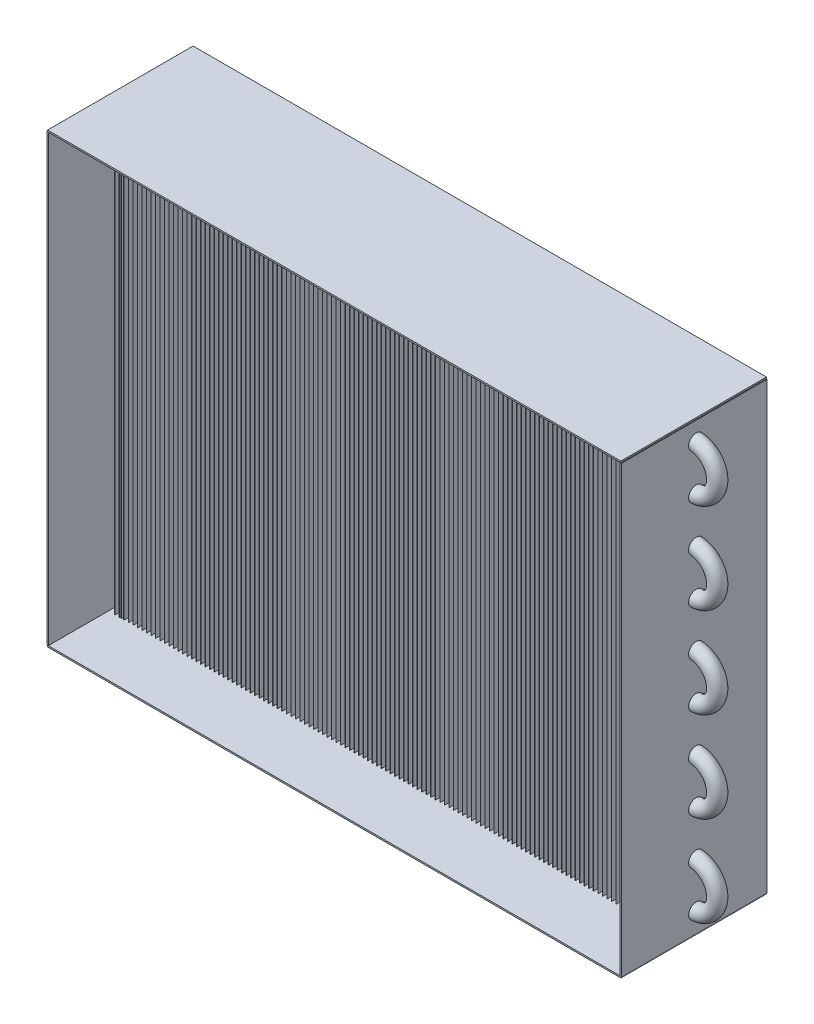
SolidWorks part; units mm, degrees
ref_plane "Front Plane" through (0, 0, 0) normal (0, 0, 1) x (1, 0, 0)
ref_plane "Top Plane" through (0, 0, 0) normal (0, 1, 0) x (1, 0, 0)
ref_plane "Right Plane" through (0, 0, 0) normal (1, 0, 0) x (0, 0, -1)
sketch "Sketch2" plane through (0, 0, 0) normal (0, 0, 1) x (1, 0, 0)
  line L0 (0, 16.0001) -> (380, 16.0001)
  line L2 (380, -13.9999) -> (0, -13.9999)
  line L4 (0, -43.9999) -> (380, -43.9999)
  line L6 (380, -73.9999) -> (0, -73.9999)
  line L8 (0, -103.9999) -> (380, -103.9999)
  line L10 (380, -133.9999) -> (0, -133.9999)
  line L12 (0, -163.9999) -> (380, -163.9999)
  line L14 (380, -193.9999) -> (0, -193.9999)
  line L16 (0, -223.9999) -> (380, -223.9999)
  line L18 (380, -253.9999) -> (0, -253.9999)
  arc A0 (380, -13.9999) -> (380, 16.0001) centre (380, 1.0001) ccw
  arc A1 (380, -73.9999) -> (380, -43.9999) centre (380, -58.9999) ccw
  arc A2 (380, -133.9999) -> (380, -103.9999) centre (380, -118.9999) ccw
  arc A3 (380, -193.9999) -> (380, -163.9999) centre (380, -178.9999) ccw
  arc A4 (380, -253.9999) -> (380, -223.9999) centre (380, -238.9999) ccw
  arc A5 (0, -193.9999) -> (0, -223.9999) centre (0, -208.9999) ccw
  arc A6 (0, -133.9999) -> (0, -163.9999) centre (0, -148.9999) ccw
  arc A7 (0, -73.9999) -> (0, -103.9999) centre (0, -88.9999) ccw
  arc A8 (0, -13.9999) -> (0, -43.9999) centre (0, -28.9999) ccw
sweep "Sweep1" add path "Sketch2" circular profile diameter 10 parameters "D3"=10
ref_plane "Plane1" through (0, 0, 0) normal (-1, 0, 0) x (0, 0, 1)
sketch "Sketch11" plane through (0, 0, 0) normal (-1, 0, 0) x (0, 0, 1)
  line L1 (-47.2003, 28.3122) -> (49.5408, 28.3122)
  line L2 (-47.2003, 28.3122) -> (-47.2003, -267.1774)
  line L3 (-47.2003, -267.1774) -> (49.5408, -267.1774)
  line L4 (49.5408, 28.3122) -> (49.5408, -267.1774)
ref_plane "Plane2" through (380, 0, 0) normal (1, 0, 0) x (0, 0, -1)
sketch "Sketch12" plane through (380, 0, 0) normal (1, 0, 0) x (0, 0, -1)
  line L1 (-49.5408, 28.3122) -> (47.2003, 28.3122)
  line L2 (-49.5408, 28.3122) -> (-49.5408, -267.1774)
  line L3 (-49.5408, -267.1774) -> (47.2003, -267.1774)
  line L4 (47.2003, 28.3122) -> (47.2003, -267.1774)
extrude "Boss-Extrude1" add sketch "Sketch12" along normal blind 1
extrude "Boss-Extrude2" add sketch "Sketch11" along normal blind 1 contours L2 L3 L4 L1
sketch "Sketch13" plane through (0, 0, 0) normal (-1, 0, 0) x (0, 0, 1)
  line L0 (0, -9.0249) -> (0, 15.9751)
  circle A0 centre (0, 15.9751) radius 5
  spline S1 degree 3 poles (-2.1721, -18.5634) (-1.5588, -18.8112) (-1.2431, -18.9036) (-0.5936, -19.0256) (-0.2669, -19.0536) (0.2222, -19.0478) (0.3852, -19.0378) (0.7115, -19.0017) (0.8755, -18.9752) (1.3573, -18.8726) (1.668, -18.7736) (2.2686, -18.5152) (2.5604, -18.3538) (3.0985, -17.983) (3.3478, -17.7727) (3.6916, -17.4193) (3.8014, -17.2947) (4.0059, -17.0383) (4.1013, -16.9057) (4.3676, -16.4955) (4.519, -16.2039) (4.7638, -15.5911) (4.8545, -15.2774) (4.9744, -14.6359) (5.0034, -14.3043) (4.996, -13.649) (4.9606, -13.3249) (4.8263, -12.6838) (4.7263, -12.3662) (4.4703, -11.7657) (4.3139, -11.4791) (3.9421, -10.9343) (3.7306, -10.6823) (3.265, -10.2257) (3.0072, -10.0182) (2.4566, -9.6585) (2.1673, -9.5079) (1.561, -9.2639) (1.2409, -9.1705) (0.5982, -9.0501) (0.2733, -9.0216) (-0.2194, -9.0271) (-0.3851, -9.0371) (-0.7114, -9.0732) (-0.8727, -9.0991) (-1.3513, -9.2002) (-1.6642, -9.2988) (-2.2712, -9.559) (-2.5571, -9.7168) (-3.0951, -10.086) (-3.3497, -10.3002) (-3.8072, -10.7697) (-4.0108, -11.0243) (-4.3678, -11.5732) (-4.5211, -11.869) (-4.7632, -12.4752) (-4.8544, -12.7886) (-4.9753, -13.4365) (-5.0034, -13.7648) (-4.9959, -14.4168) (-4.9602, -14.7452) (-4.8247, -15.3894) (-4.7266, -15.7005) (-4.4708, -16.3016) (-4.311, -16.594) (-3.9423, -17.1346) (-3.7334, -17.3849) (-3.3825, -17.7301) (-3.2585, -17.8406) (-3.0027, -18.0468) (-2.8705, -18.143) (-2.4614, -18.4114) (-2.1721, -18.5634) (-1.5588, -18.8112) (-1.2431, -18.9036) knots -0.03125 -0.03125 0 0 0.03125 0.03125 0.0625 0.0625 0.078125 0.078125 0.09375 0.09375 0.125 0.125 0.15625 0.15625 0.1875 0.1875 0.203125 0.203125 0.21875 0.21875 0.25 0.25 0.28125 0.28125 0.3125 0.3125 0.34375 0.34375 0.375 0.375 0.40625 0.40625 0.4375 0.4375 0.46875 0.46875 0.5 0.5 0.53125 0.53125 0.5625 0.5625 0.578125 0.578125 0.59375 0.59375 0.625 0.625 0.65625 0.65625 0.6875 0.6875 0.71875 0.71875 0.75 0.75 0.78125 0.78125 0.8125 0.8125 0.84375 0.84375 0.875 0.875 0.90625 0.90625 0.9375 0.9375 0.953125 0.953125 0.96875 0.96875 1 1 1.03125 1.03125 1.0625 only from (-1.8655, -18.6873) to (-1.8655, -18.6873) construction
sketch "Sketch15" plane through (0, 0, 0) normal (-1, 0, 0) x (0, 0, 1)
  line L0 (0, -9.0249) -> (0, 15.9751)
  circle A0 centre (0, 15.9751) radius 5
  spline S0 degree 3 poles (-2.1721, -18.5634) (-1.5588, -18.8112) (-1.2431, -18.9036) (-0.5936, -19.0256) (-0.2669, -19.0536) (0.2222, -19.0478) (0.3852, -19.0378) (0.7115, -19.0017) (0.8755, -18.9752) (1.3573, -18.8726) (1.668, -18.7736) (2.2686, -18.5152) (2.5604, -18.3538) (3.0985, -17.983) (3.3478, -17.7727) (3.6916, -17.4193) (3.8014, -17.2947) (4.0059, -17.0383) (4.1013, -16.9057) (4.3676, -16.4955) (4.519, -16.2039) (4.7638, -15.5911) (4.8545, -15.2774) (4.9744, -14.6359) (5.0034, -14.3043) (4.996, -13.649) (4.9606, -13.3249) (4.8263, -12.6838) (4.7263, -12.3662) (4.4703, -11.7657) (4.3139, -11.4791) (3.9421, -10.9343) (3.7306, -10.6823) (3.265, -10.2257) (3.0072, -10.0182) (2.4566, -9.6585) (2.1673, -9.5079) (1.561, -9.2639) (1.2409, -9.1705) (0.5982, -9.0501) (0.2733, -9.0216) (-0.2194, -9.0271) (-0.3851, -9.0371) (-0.7114, -9.0732) (-0.8727, -9.0991) (-1.3513, -9.2002) (-1.6642, -9.2988) (-2.2712, -9.559) (-2.5571, -9.7168) (-3.0951, -10.086) (-3.3497, -10.3002) (-3.8072, -10.7697) (-4.0108, -11.0243) (-4.3678, -11.5732) (-4.5211, -11.869) (-4.7632, -12.4752) (-4.8544, -12.7886) (-4.9753, -13.4365) (-5.0034, -13.7648) (-4.9959, -14.4168) (-4.9602, -14.7452) (-4.8247, -15.3894) (-4.7266, -15.7005) (-4.4708, -16.3016) (-4.311, -16.594) (-3.9423, -17.1346) (-3.7334, -17.3849) (-3.3825, -17.7301) (-3.2585, -17.8406) (-3.0027, -18.0468) (-2.8705, -18.143) (-2.4614, -18.4114) (-2.1721, -18.5634) (-1.5588, -18.8112) (-1.2431, -18.9036) knots -0.03125 -0.03125 0 0 0.03125 0.03125 0.0625 0.0625 0.078125 0.078125 0.09375 0.09375 0.125 0.125 0.15625 0.15625 0.1875 0.1875 0.203125 0.203125 0.21875 0.21875 0.25 0.25 0.28125 0.28125 0.3125 0.3125 0.34375 0.34375 0.375 0.375 0.40625 0.40625 0.4375 0.4375 0.46875 0.46875 0.5 0.5 0.53125 0.53125 0.5625 0.5625 0.578125 0.578125 0.59375 0.59375 0.625 0.625 0.65625 0.65625 0.6875 0.6875 0.71875 0.71875 0.75 0.75 0.78125 0.78125 0.8125 0.8125 0.84375 0.84375 0.875 0.875 0.90625 0.90625 0.9375 0.9375 0.953125 0.953125 0.96875 0.96875 1 1 1.03125 1.03125 1.0625 only from (-1.8655, -18.6873) to (-1.8655, -18.6873) construction
extrude "Cut-Extrude2" cut sketch "Sketch15" along normal blind 1 contours A0
sketch "Sketch16" plane through (0, 0, 0) normal (-1, 0, 0) x (0, 0, 1)
  line L0 (0, -228.9749) -> (0, -253.9749)
  circle A0 centre (0, -253.9749) radius 5
  spline S0 degree 3 poles (-3.0361, -227.96) (-2.4848, -228.3255) (-2.194, -228.4793) (-1.5824, -228.7291) (-1.2678, -228.8223) (-0.7875, -228.9151) (-0.6258, -228.9383) (-0.2991, -228.9687) (-0.1332, -228.9758) (0.3597, -228.9728) (0.684, -228.9386) (1.3244, -228.8072) (1.6429, -228.7083) (2.2449, -228.4539) (2.5316, -228.2983) (2.9396, -228.0216) (3.0722, -227.9217) (3.3243, -227.7117) (3.4444, -227.6011) (3.7877, -227.2527) (3.9946, -226.9974) (4.3571, -226.446) (4.5086, -226.1568) (4.7542, -225.5522) (4.8487, -225.2331) (4.972, -224.5894) (5.0018, -224.2648) (4.998, -223.6098) (4.9634, -223.2787) (4.8324, -222.6392) (4.7364, -222.3272) (4.4815, -221.7191) (4.3248, -221.4296) (3.9605, -220.8887) (3.75, -220.6336) (3.2832, -220.17) (3.0302, -219.9639) (2.4859, -219.6024) (2.1914, -219.4461) (1.5863, -219.1981) (1.2739, -219.1044) (0.7902, -219.0102) (0.6259, -218.9866) (0.299, -218.9561) (0.1358, -218.949) (-0.3533, -218.9517) (-0.6796, -218.9854) (-1.3265, -219.1185) (-1.6383, -219.2159) (-2.2392, -219.4699) (-2.5315, -219.6288) (-3.0737, -219.9973) (-3.3241, -220.2061) (-3.7837, -220.6723) (-3.9931, -220.9314) (-4.352, -221.4768) (-4.5043, -221.7655) (-4.7529, -222.3757) (-4.8465, -222.6918) (-4.9704, -223.332) (-5.0015, -223.6608) (-4.9984, -224.3191) (-4.9649, -224.6437) (-4.8351, -225.2838) (-4.7372, -225.6024) (-4.4846, -226.206) (-4.33, -226.4931) (-4.0553, -226.9015) (-3.9559, -227.0345) (-3.7465, -227.2878) (-3.6363, -227.4085) (-3.2891, -227.7532) (-3.0361, -227.96) (-2.4848, -228.3255) (-2.194, -228.4793) knots -0.03125 -0.03125 0 0 0.03125 0.03125 0.0625 0.0625 0.078125 0.078125 0.09375 0.09375 0.125 0.125 0.15625 0.15625 0.1875 0.1875 0.203125 0.203125 0.21875 0.21875 0.25 0.25 0.28125 0.28125 0.3125 0.3125 0.34375 0.34375 0.375 0.375 0.40625 0.40625 0.4375 0.4375 0.46875 0.46875 0.5 0.5 0.53125 0.53125 0.5625 0.5625 0.578125 0.578125 0.59375 0.59375 0.625 0.625 0.65625 0.65625 0.6875 0.6875 0.71875 0.71875 0.75 0.75 0.78125 0.78125 0.8125 0.8125 0.84375 0.84375 0.875 0.875 0.90625 0.90625 0.9375 0.9375 0.953125 0.953125 0.96875 0.96875 1 1 1.03125 1.03125 1.0625 only from (-2.7604, -228.1428) to (-2.7604, -228.1428) construction
ref_plane "Plane3" through (0, 28.3122, 0) normal (0, 1, 0) x (1, 0, 0)
sketch "Sketch17" plane through (0, 28.3122, 0) normal (0, 1, 0) x (1, 0, 0)
  line L0 (-1, -49.5408) -> (0, -49.5408) construction
  line L1 (-0.5, -49.5408) -> (380.5, -49.5408)
  line L2 (-0.5, -49.5408) -> (-0.5, 47.2003)
  line L3 (-0.5, 47.2003) -> (380.5, 47.2003)
  line L4 (380.5, -49.5408) -> (380.5, 47.2003)
  line L5 (381, 47.2003) -> (380, 47.2003) construction
extrude "Boss-Extrude4" add sketch "Sketch17" along normal blind 1
ref_plane "Plane5" through (0, -267.1774, 0) normal (0, -1, 0) x (-1, 0, 0)
sketch "Sketch18" plane through (0, -267.1774, 0) normal (0, -1, 0) x (-1, 0, 0)
  line L0 (1, 47.2003) -> (0, 47.2003) construction
  line L1 (0.5, 47.2003) -> (-380.5, 47.2003)
  line L2 (0.5, 47.2003) -> (0.5, -49.5408)
  line L3 (0.5, -49.5408) -> (-380.5, -49.5408)
  line L4 (-380.5, 47.2003) -> (-380.5, -49.5408)
  line L5 (-381, -49.5408) -> (-380, -49.5408) construction
extrude "Boss-Extrude5" add sketch "Sketch18" along normal blind 1
ref_plane "Plane6" through (10, 0, 0) normal (1, 0, 0) x (0, 0, -1)
sketch "Sketch19" plane through (10, 0, 0) normal (1, 0, 0) x (0, 0, -1)
  line L1 (-15.4034, 22.788) -> (15.954, 22.788)
  line L2 (-15.4034, 22.788) -> (-15.4034, -261.4307)
  line L3 (-15.4034, -261.4307) -> (15.954, -261.4307)
  line L4 (15.954, 22.788) -> (15.954, -261.4307)
extrude "Boss-Extrude6" add sketch "Sketch19" along normal blind 0.2
ref_plane "Plane7" through (12.2, 0, 0) normal (1, 0, 0) x (0, 0, -1)
mirror "Mirror1" about plane through (12.2, 0, 0) normal (1, 0, 0) of "Boss-Extrude6"
pattern_linear "LPattern2" count 122 spacing 3 along (1, 0, 0) of "Boss-Extrude6"
